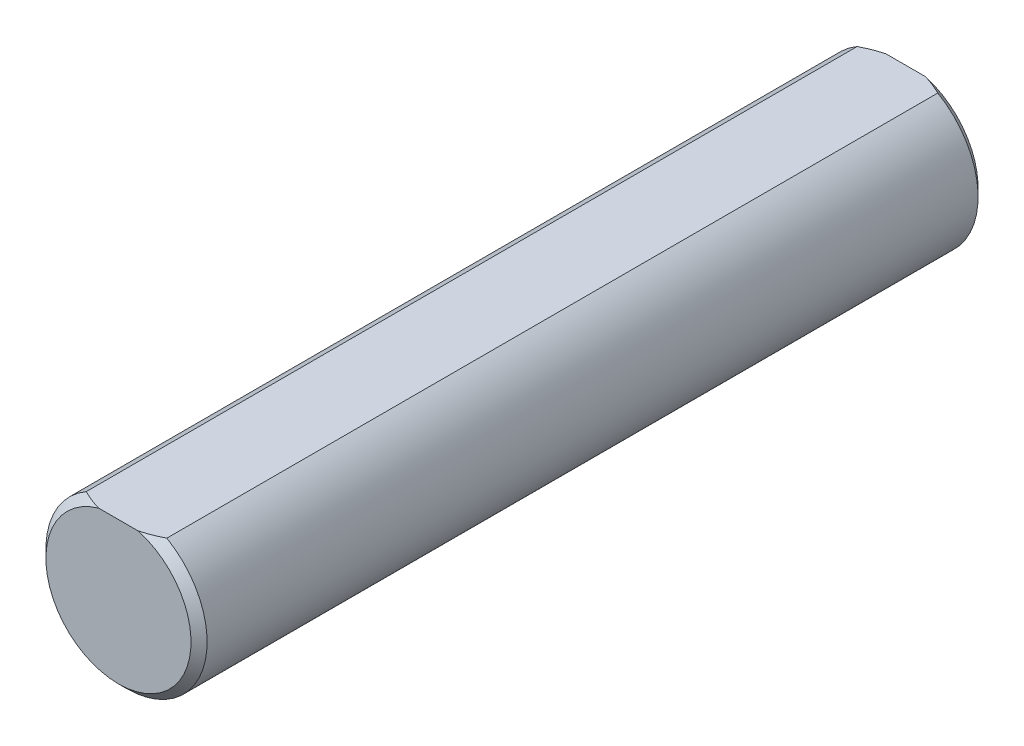
SolidWorks part; units mm, degrees
ref_plane "Front Plane" through (0, 0, 0) normal (0, 0, 1) x (1, 0, 0)
ref_plane "Top Plane" through (0, 0, 0) normal (0, 1, 0) x (1, 0, 0)
ref_plane "Right Plane" through (0, 0, 0) normal (1, 0, 0) x (0, 0, -1)
sketch "Sketch1" plane through (0, 0, 0) normal (0, 0, 1) x (1, 0, 0)
  line L0 (-1.5875, 2.7496) -> (1.5875, 2.7496) construction
  circle A1 centre (0, 0) radius 3.175 construction
  dimension "Diameter" = 6.35
  dimension "Flat Width" = 3.175
sketch "Sketch2" plane through (0, 0, 0) normal (1, 0, 0) x (0, 0, -1)
  line L0 (-15.5, 3.175) -> (15.5, 3.175) construction
  line L1 (0, 3.175) -> (0, -3.175) construction
  line L2 (0, 3.175) -> (0, -3.175) construction
  line L3 (-15.5, 3.175) -> (-15.5, -3.175) construction
  line L4 (-15.5, -3.175) -> (15.5, -3.175) construction
  point P2 (0, 3.175)
  point P3 (2.8, 3.175)
  point P4 (-2.8, 3.175)
  dimension "Length" = 31
  dimension "D2" = 12.7
  dimension "D1" = 12.7
  dimension "D-Profile Length" = 31
sketch "Sketch3" plane through (0, 0, 0) normal (0, 0, 1) x (1, 0, 0)
  circle A1 centre (0, 0) radius 3.175 construction
  circle A3 centre (0, 0) radius 3.175
extrude "Boss-Extrude2" add sketch "Sketch3" along normal up to vertex (15.5 mm away) and the other way up to vertex (15.5 mm away) up to point (0, 3.175, 15.5) other way up to point (0, 3.175, -15.5)
sketch "Sketch10" plane through (0, 0, 0) normal (0, 0, 1) x (1, 0, 0)
  line L0 (-1.5875, 2.7496) -> (1.5875, 2.7496)
  line L1 (0, 0) -> (0, 3.175) construction
  circle A0 centre (0, 0) radius 3.175 construction
  circle A1 centre (0, 0) radius 3.175 construction
  arc A2 (-1.5875, 2.7496) -> (1.5875, 2.7496) centre (0, 0) cw
extrude "Cut-Extrude5" cut sketch "Sketch10" against normal through all both and the other way through all
chamfer "Chamfer1" distance 0.3175 angle 45 2 edges at (0, -3.175, 15.5) (0, -3.175, -15.5)
equation "\"D1@Chamfer1\"= \"Diameter@Sketch1\" / 20"
equation "\"D1@Sketch2\"=\"Diameter@Sketch1\"*2"
equation "\"D2@Sketch2\"=\"D1@Sketch2\""
equation "\"D-Profile Length@Sketch2\"=\"Length@Sketch2\""
